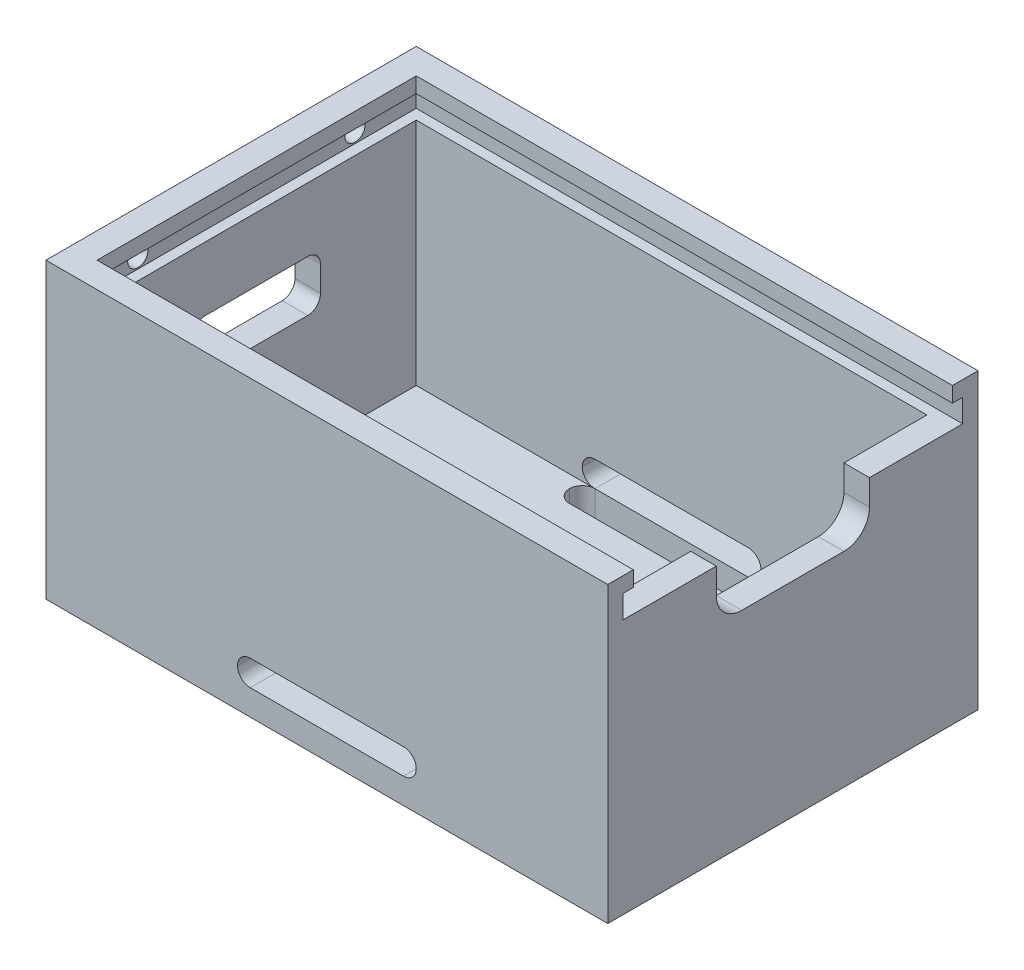
SolidWorks part; units mm, degrees
ref_plane "前视基准面" through (0, 0, 0) normal (0, 0, 1) x (1, 0, 0)
ref_plane "上视基准面" through (0, 0, 0) normal (0, 1, 0) x (1, 0, 0)
ref_plane "右视基准面" through (0, 0, 0) normal (1, 0, 0) x (0, 0, -1)
sketch "草图1" plane through (0, 0, 0) normal (0, 1, 0) x (1, 0, 0)
  line L1 (-22, 14.5) -> (22, 14.5)
  line L2 (-22, 14.5) -> (-22, -14.5)
  line L3 (-22, -14.5) -> (22, -14.5)
  line L4 (22, 14.5) -> (22, -14.5)
  line L5 (-22, 14.5) -> (22, -14.5) construction
  line L6 (-22, -14.5) -> (22, 14.5) construction
  point P0 (0, 0)
  dimension "D1" = 44
  dimension "D2" = 29
extrude "凸台-拉伸1" add sketch "草图1" along normal blind 23
shell "抽壳1" thickness 2 removed face at (0, 23, 0)
sketch "草图2" plane through (22, 0, 0) normal (1, 0, 0) x (0, 0, -1)
  line L0 (-14.5, 23) -> (14.5, 23) construction
  line L1 (-6, 23) -> (6, 23)
  line L2 (-6, 23) -> (-6, 16)
  line L3 (-6, 16) -> (6, 16)
  line L4 (6, 23) -> (6, 16)
  point P6 (0, 23)
  dimension "D1" = 7
  dimension "D2" = 12
extrude "切除-拉伸1" cut sketch "草图2" against normal up to next
sketch "草图3" plane through (-20, 0, 0) normal (1, 0, 0) x (0, 0, -1)
  line L0 (12.5, 2) -> (-12.5, 2) construction
  line L1 (-5, 15) -> (5, 15)
  line L2 (-5, 15) -> (-5, 11)
  line L3 (-5, 11) -> (5, 11)
  line L4 (5, 15) -> (5, 11)
  point P6 (0, 15)
  dimension "D1" = 9
  dimension "D2" = 10
  dimension "D3" = 4
extrude "切除-拉伸2" cut sketch "草图3" against normal up to next
fillet "圆角1" radius 1 4 edges at (-21, 15, 5) (-21, 11, 5) (-21, 11, -5) (-21, 15, -5)
fillet "圆角2" radius 2 2 edges at (21, 16, -6) (21, 16, 6)
sketch "草图4" plane through (22, 0, 0) normal (1, 0, 0) x (0, 0, -1)
  line L0 (-14.5, 23) -> (-6, 23) construction
  line L1 (-12.5, 23) -> (12.5, 23)
  line L2 (-12.5, 23) -> (-12.5, 20)
  line L3 (-12.5, 20) -> (12.5, 20)
  line L4 (12.5, 23) -> (12.5, 20)
  line L5 (-12.5, 23) -> (-12.5, 2) construction
  line L6 (12.5, 23) -> (12.5, 2) construction
  dimension "D1" = 3
extrude "切除-拉伸3" cut sketch "草图4" against normal up to next (42 mm away)
sketch "草图5" plane through (22, 0, 0) normal (1, 0, 0) x (0, 0, -1)
  line L0 (-14.5, 23) -> (-14.5, 0) construction
  line L1 (-13.3, 21.8) -> (13.3, 21.8)
  line L2 (-13.3, 21.8) -> (-13.3, 20)
  line L3 (-13.3, 20) -> (13.3, 20)
  line L4 (13.3, 21.8) -> (13.3, 20)
  line L5 (14.5, 23) -> (14.5, 0) construction
  line L6 (-14.5, 23) -> (-12.5, 23) construction
  dimension "D1" = 1.2
  dimension "D2" = 1.2
  dimension "D3" = 1.2
  dimension "D4" = 1.8
extrude "切除-拉伸4" cut sketch "草图5" against normal offset from surface (42.8 mm away) 0.8 up to face at (-20, 13, 0) offset beyond the face yes
sketch "草图6" plane through (-22, 0, 0) normal (-1, 0, 0) x (0, 0, 1)
  line L0 (-14.5, 23) -> (-14.5, 0) construction
  line L1 (14.5, 23) -> (14.5, 0) construction
  line L3 (13.3, 20) -> (13.3, 21.8) construction
  circle A0 centre (-8.5, 20.9) radius 0.8
  circle A1 centre (8.5, 20.9) radius 0.8
  point P10 (13.3, 20.9)
  dimension "D1" = 1.6
  dimension "D2" = 6
  dimension "D3" = 6
extrude "切除-拉伸5" cut sketch "草图6" against normal up to next
sketch "草图8" plane through (0, 0, 0) normal (0, -1, 0) x (1, 0, 0)
  line L0 (22, -14.5) -> (-22, -14.5) construction
  line L1 (-7, -10.5) -> (7, -10.5)
  line L2 (-7, -10.5) -> (-7, -12.5)
  line L3 (-7, -12.5) -> (7, -12.5)
  line L4 (7, -10.5) -> (7, -12.5)
  point P6 (0, -10.5)
  dimension "D1" = 14
  dimension "D2" = 2
  dimension "D3" = 2
extrude "切除-拉伸6" cut sketch "草图8" against normal up to next
sketch "草图9" plane through (0, 0, -14.5) normal (0, 0, -1) x (-1, 0, 0)
  line L0 (-22, 0) -> (22, 0) construction
  line L1 (-7, 4) -> (7, 4)
  line L2 (-7, 4) -> (-7, 2)
  line L3 (-7, 2) -> (7, 2)
  line L4 (7, 4) -> (7, 2)
  point P6 (0, 4)
  dimension "D1" = 14
  dimension "D2" = 2
  dimension "D3" = 2
extrude "切除-拉伸7" cut sketch "草图9" against normal up to next
fillet "圆角3" radius 1 4 edges at (-7, 4, -13.5) (-7, 2, -13.5) (7, 2, -13.5) (7, 4, -13.5)
fillet "圆角4" radius 1 4 edges at (-7, 1, -12.5) (-7, 1, -10.5) (7, 1, -12.5) (7, 1, -10.5)
mirror "镜向1" about plane through (0, 0, 0) normal (0, 0, 1) of "圆角4", "圆角3", "切除-拉伸6", "切除-拉伸7"
